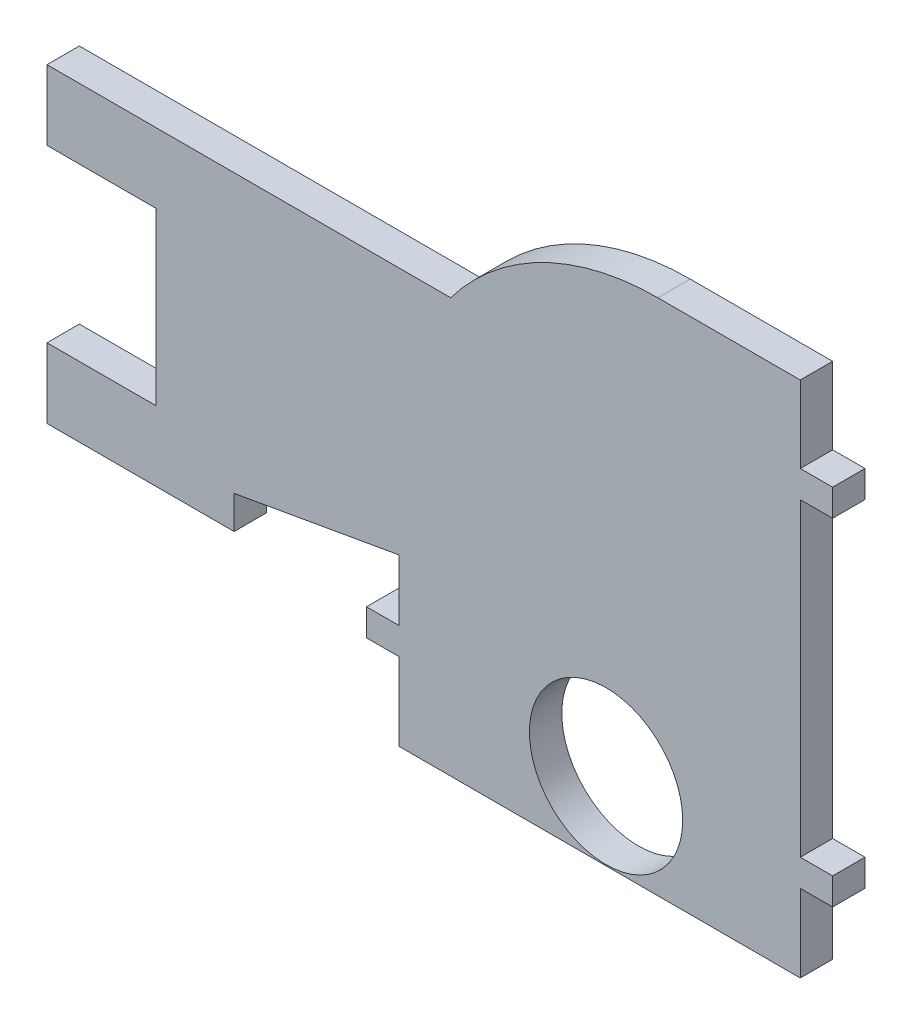
SolidWorks part; units mm, degrees
material "Balsa"
ref_plane "Front Plane" through (0, 0, 0) normal (0, 0, 1) x (1, 0, 0)
ref_plane "Top Plane" through (0, 0, 0) normal (0, 1, 0) x (1, 0, 0)
ref_plane "Right Plane" through (0, 0, 0) normal (1, 0, 0) x (0, 0, -1)
sketch "Sketch1" plane through (0, 0, 0) normal (0, 0, 1) x (1, 0, 0)
  line L0 (0, -1000.1535) -> (0, 48999.8465) construction
  line L1 (-7.62, 16.51) -> (-27.4189, 16.51)
  line L2 (-1000, 0) -> (49000, 0) construction
  line L3 (9.525, 16.51) -> (11.1125, 16.51)
  line L4 (2.54, 21.59) -> (9.525, 21.59)
  line L5 (-10.16, 8.89) -> (-10.16, -3.81)
  line L6 (-10.16, -3.81) -> (9.525, -3.81)
  line L7 (9.525, 21.59) -> (9.525, -3.81)
  line L8 (-11.7475, 0) -> (-10.16, 0)
  line L9 (-11.7475, 0) -> (-11.7475, 1.3208)
  line L10 (-11.7475, 1.3208) -> (-10.16, 1.3208)
  line L11 (-10.16, 0) -> (-10.16, 1.3208)
  line L12 (9.525, 0) -> (11.1125, 0)
  line L13 (9.525, 0) -> (9.525, 1.3208)
  line L14 (9.525, 1.3208) -> (11.1125, 1.3208)
  line L15 (11.1125, 0) -> (11.1125, 1.3208)
  line L16 (9.525, 16.51) -> (9.525, 17.8308)
  line L17 (9.525, 17.8308) -> (11.1125, 17.8308)
  line L18 (11.1125, 16.51) -> (11.1125, 17.8308)
  line L19 (-27.4189, 16.51) -> (-27.4189, 1.27)
  line L20 (-27.4189, 1.27) -> (-10.16, 4.318)
  line L21 (-27.4189, 13.081) -> (-22.0849, 13.081)
  line L22 (-22.0849, 13.081) -> (-22.0849, 4.699)
  line L23 (-22.0849, 4.699) -> (-27.4189, 4.699)
  line L24 (-27.4189, 1.27) -> (-18.2418, 1.27)
  line L25 (-18.2418, 1.27) -> (-18.2418, 2.8907)
  circle A0 centre (0, 0) radius 3.7592
  arc A3 (2.54, 21.59) -> (-10.16, 8.89) centre (2.54, 8.89) ccw
  dimension "D1" = 7.5184
  dimension "D4" = 3.81
  dimension "D9" = 12.7
  dimension "D10" = 1.5875
  dimension "D2" = 25.4
  dimension "D6" = 9.525
  dimension "D8" = 19.685
  dimension "D12" = 1.3208
  dimension "D13" = 1.3208
  dimension "D14" = 1.5875
  dimension "D15" = 2
extrude "Boss-Extrude1" add sketch "Sketch1" along normal blind 1.5875 contours L4 A3 L5 L6 L7 A0 | L10 L9 L8 L5 | L3 L18 L17 L7 | L12 L15 L14 L7 | A3 L1 L19 L20 L5 | L24 L25 L20 region at (-17.5342, 9.9456, 0) region at (0.225, 9.0166, 0) region at (10.3187, 17.1704, 0) region at (-10.9538, 0.6604, 0) region at (-21.3008, 1.8102, 0) region at (10.3187, 0.6604, 0)
move or copy body "Body-Move/Copy1" [suppressed] bodies to move or copy 101
